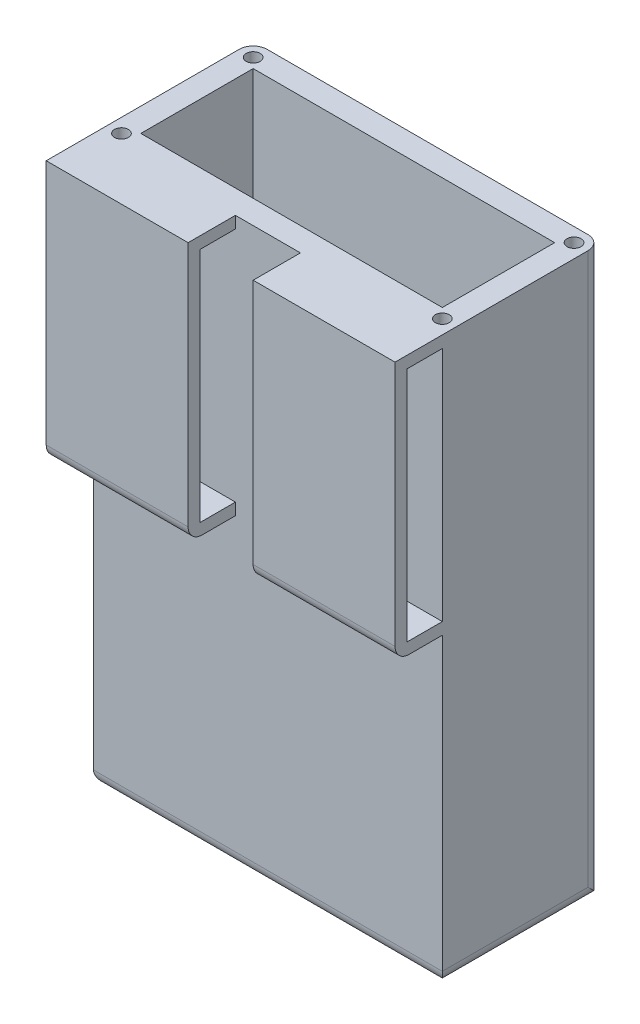
SolidWorks part; units mm, degrees
ref_plane "Front Plane" through (0, 0, 0) normal (0, 0, 1) x (1, 0, 0)
ref_plane "Top Plane" through (0, 0, 0) normal (0, 1, 0) x (1, 0, 0)
ref_plane "Right Plane" through (0, 0, 0) normal (1, 0, 0) x (0, 0, -1)
sketch "Sketch1" plane through (0, 0, 0) normal (0, 1, 0) x (1, 0, 0)
  line L1 (0, 0) -> (74.93, 0)
  line L2 (0, 0) -> (0, 34.29)
  line L3 (0, 34.29) -> (74.93, 34.29)
  line L4 (74.93, 0) -> (74.93, 34.29)
  dimension "D1" = 74.93
  dimension "D2" = 34.29
extrude "Boss-Extrude1" add sketch "Sketch1" along normal blind 87.122
shell "Shell1" thickness 2.54 removed face at (37.465, 43.561, -34.29)
sketch "Sketch12" plane through (0, 87.122, 0) normal (0, 1, 0) x (1, 0, 0)
  line L1 (0, 0) -> (74.93, 0)
  line L2 (0, 0) -> (0, 34.29)
  line L3 (0, 34.29) -> (74.93, 34.29)
  line L4 (74.93, 0) -> (74.93, 34.29)
extrude "Boss-Extrude6" add sketch "Sketch12" along normal blind 34.29
shell "Shell2" thickness 5.08 removed face at (37.465, 121.412, -17.145)
sketch "Sketch18" plane through (0, 89.662, 0) normal (0, 1, 0) x (1, 0, 0)
  line L0 (5.08, 5.08) -> (69.85, 5.08) construction
  line L1 (34.925, 5.08) -> (22.225, 5.08)
  line L2 (34.925, 5.08) -> (34.925, 14.605)
  line L3 (34.925, 14.605) -> (22.225, 14.605)
  line L4 (22.225, 5.08) -> (22.225, 14.605)
  line L5 (69.85, 5.08) -> (69.85, 29.21) construction
  line L6 (69.85, 29.21) -> (5.08, 29.21) construction
  line L7 (69.85, 22.21) -> (64.85, 22.21)
  line L8 (69.85, 22.21) -> (69.85, 12.08)
  line L9 (69.85, 12.08) -> (64.85, 12.08)
  line L10 (64.85, 22.21) -> (64.85, 12.08)
  dimension "D1" = 34.925
  dimension "D2" = 47.625
  dimension "D3" = 9.525
  dimension "D4" = 5
  dimension "D5" = 7
  dimension "D6" = 7
extrude "Cut-Extrude13" cut sketch "Sketch18" against normal up to next
sketch "Sketch20" plane through (0, 121.412, 0) normal (0, 1, 0) x (1, 0, 0)
  line L0 (0, 34.29) -> (0, 0) construction
  line L2 (74.93, 34.29) -> (0, 34.29) construction
  line L3 (0, 0) -> (74.93, 0) construction
  line L4 (74.93, 0) -> (74.93, 34.29) construction
  circle A0 centre (3, 31.29) radius 1.5
  circle A1 centre (3, 3) radius 1.5
  circle A2 centre (71.93, 3) radius 1.5
  circle A3 centre (71.93, 31.29) radius 1.5
  point P8 (0, 0)
  point P9 (0, 0)
  point P10 (0, 0)
  point P13 (0, 0)
  point P15 (7.3304, 34.29)
  dimension "D1" = 3
  dimension "D2" = 3
  dimension "D3" = 3
  dimension "D4" = 3
  dimension "D5" = 3
  dimension "D6" = 3
  dimension "D7" = 3
  dimension "D8" = 3
extrude "Cut-Extrude14" cut sketch "Sketch20" against normal blind 20
sketch "Sketch15" plane through (0, 0, 0) normal (0, 0, 1) x (1, 0, 0)
  line L1 (0, 121.412) -> (30.48, 121.412)
  line L2 (0, 121.412) -> (0, 65.532)
  line L3 (0, 65.532) -> (30.48, 65.532)
  line L4 (30.48, 121.412) -> (30.48, 65.532)
  line L5 (74.93, 121.412) -> (44.45, 121.412)
  line L6 (74.93, 121.412) -> (74.93, 65.532)
  line L7 (74.93, 65.532) -> (44.45, 65.532)
  line L8 (44.45, 121.412) -> (44.45, 65.532)
  dimension "D1" = 30.48
  dimension "D2" = 30.48
  dimension "D3" = 55.88
  dimension "D4" = 55.88
extrude "Boss-Extrude8" add sketch "Sketch15" along normal blind 10.16
sketch "Sketch16" plane through (0, 0, 0) normal (-1, 0, 0) x (0, 0, 1)
  line L0 (10.16, 121.412) -> (10.16, 65.532) construction
  line L1 (7.62, 68.072) -> (0, 68.072)
  line L2 (7.62, 68.072) -> (7.62, 118.872)
  line L3 (7.62, 118.872) -> (0, 118.872)
  line L4 (0, 68.072) -> (0, 118.872)
  line L5 (10.16, 65.532) -> (0, 65.532) construction
  line L6 (-34.29, 121.412) -> (10.16, 121.412) construction
  line L8 (0, 65.532) -> (0, 0) construction
  dimension "D1" = 2.54
  dimension "D2" = 2.54
  dimension "D3" = 2.54
extrude "Cut-Extrude11" cut sketch "Sketch16" against normal through all
fillet "Fillet1" radius 3 7 edges at (59.69, 65.532, 10.16) (15.24, 65.532, 10.16) (74.93, 0, -17.145) (0, 0, -17.145) (37.465, 0, 0) (74.93, 60.706, -34.29) (0, 60.706, -34.29)
